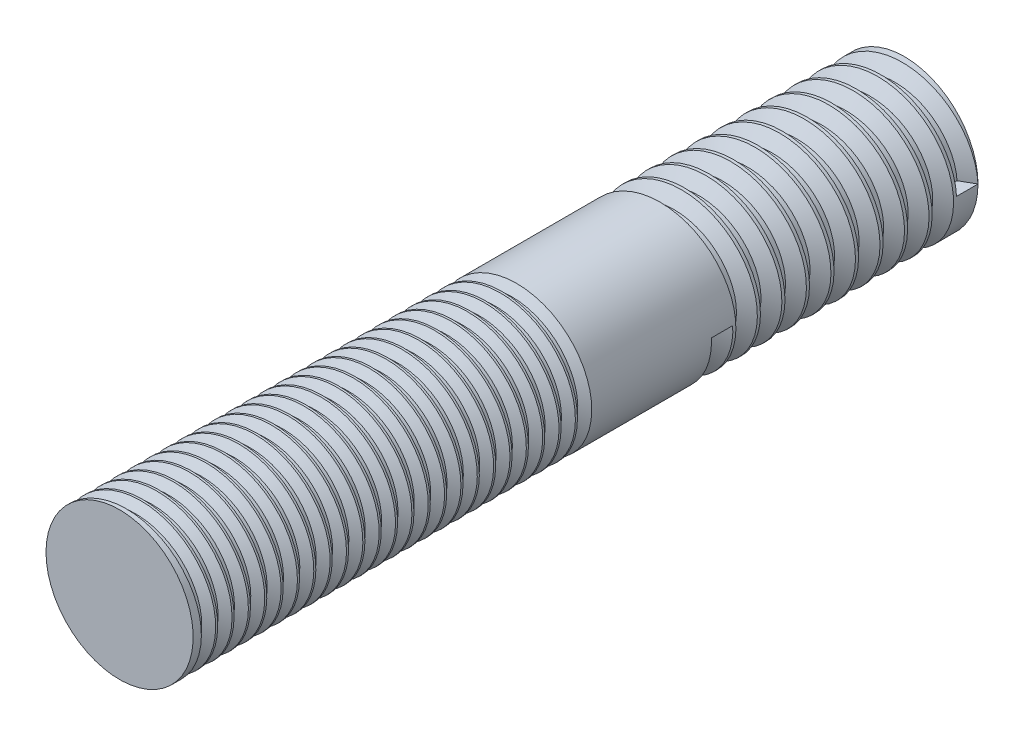
SolidWorks part; units mm, degrees
ref_plane "Front Plane" through (0, 0, 0) normal (0, 0, 1) x (1, 0, 0)
ref_plane "Top Plane" through (0, 0, 0) normal (0, 1, 0) x (1, 0, 0)
ref_plane "Right Plane" through (0, 0, 0) normal (1, 0, 0) x (0, 0, -1)
sketch "Sketch1" plane through (0, 0, 0) normal (0, 0, 1) x (1, 0, 0)
  circle A0 centre (0, 0) radius 4.7625
  dimension "D1" = 9.525
extrude "Boss-Extrude1" add sketch "Sketch1" along normal blind 50.8
thread "Thread1" pitch 1.0583 method cut profile "Thread Profile1" start angle 0, offset 0, length 25.4, pitch 1.0583, diameter 9.525
ref_plane "Plane1" through (-4.7625, 0, 50.8) normal (0, -1, 0) x (-1, 0, 0)
sketch "Thread Profile1" plane through (-4.7625, 0, 50.8) normal (0, -1, 0) x (-1, 0, 0)
  line L0 (0, 0) -> (0, 1.0583) construction
  line L11 (0, 0) -> (0, 0.926)
  line L12 (0, 0.926) -> (-0.5728, 0.5953)
  line L13 (-0.5728, 0.5953) -> (-0.5728, 0.3307)
  line L15 (-0.5728, 0.3307) -> (0, 0)
  line L17 (-0.5728, 0.463) -> (0, 0.463) construction
  point P2 (0, 0)
  dimension "Pitch" = 1.0583
  dimension "Profile_Angle" = 60
  dimension "Profile_Land" = 0.2646
  dimension "Profile_Height" = 0.5728
thread "Thread2" pitch 1.5875 method cut profile "Thread Profile2" start angle 0, offset 0, length 15.875, pitch 1.5875, diameter 9.525
ref_plane "Plane2" through (4.7625, 0, 0) normal (0, -1, 0) x (1, 0, 0)
sketch "Thread Profile2" plane through (4.7625, 0, 0) normal (0, -1, 0) x (1, 0, 0)
  line L0 (0, 0) -> (0, 1.5875) construction
  line L11 (0, 0) -> (0, 1.3891)
  line L12 (0, 1.3891) -> (-0.8593, 0.893)
  line L13 (-0.8593, 0.893) -> (-0.8593, 0.4961)
  line L15 (-0.8593, 0.4961) -> (0, 0)
  line L17 (-0.8593, 0.6945) -> (0, 0.6945) construction
  point P2 (0, 0)
  dimension "Pitch" = 1.5875
  dimension "Profile_Angle" = 60
  dimension "Profile_Land" = 0.3969
  dimension "Profile_Height" = 0.8593
